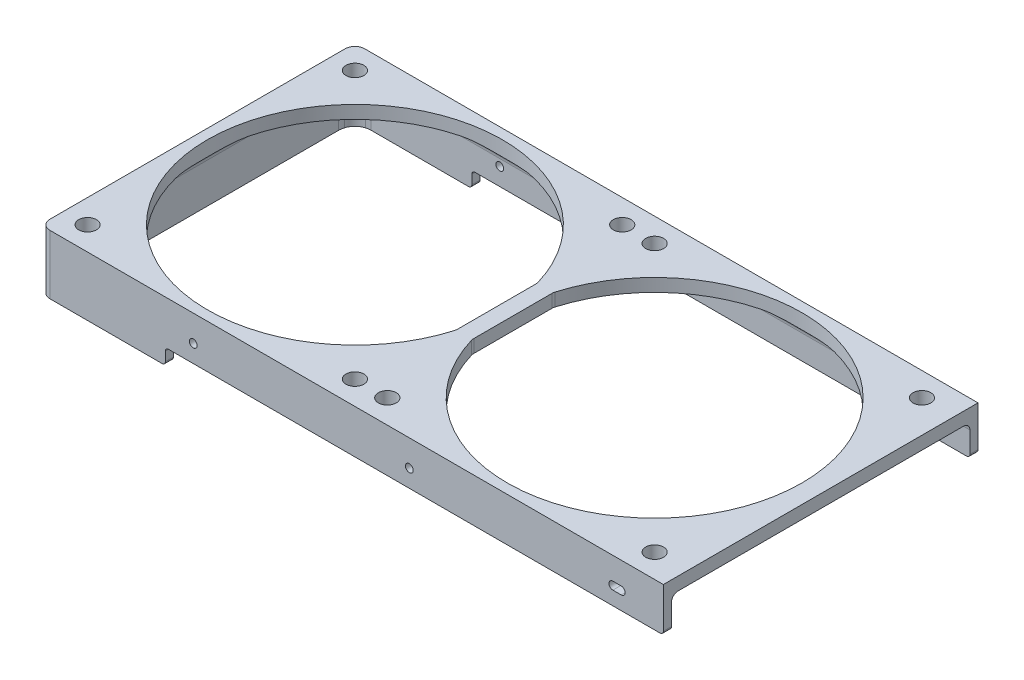
SolidWorks part; units mm, degrees
ref_plane "Front Plane" through (0, 0, 0) normal (0, 0, 1) x (1, 0, 0)
ref_plane "Top Plane" through (0, 0, 0) normal (0, 1, 0) x (1, 0, 0)
ref_plane "Right Plane" through (0, 0, 0) normal (1, 0, 0) x (0, 0, -1)
sketch "Sketch1" plane through (0, 0, 0) normal (0, 1, 0) x (1, 0, 0)
  line L1 (96.15, -48.55) -> (-96.15, -48.55)
  line L2 (96.15, -48.55) -> (96.15, 48.55)
  line L3 (96.15, 48.55) -> (-96.15, 48.55)
  line L4 (-96.15, -48.55) -> (-96.15, 48.55)
  line L5 (96.15, -48.55) -> (-96.15, 48.55) construction
  line L6 (96.15, 48.55) -> (-96.15, -48.55) construction
  point P0 (0, 0)
  dimension "D1" = 97.1
  dimension "D2" = 192.3
extrude "Boss-Extrude1" add sketch "Sketch1" along normal blind 13.5
sketch "Sketch2" plane through (0, 0, 0) normal (0, -1, 0) x (1, 0, 0)
  line L0 (96.15, 48.55) -> (96.15, -48.55) construction
  line L1 (96.15, 46.05) -> (-93.65, 46.05)
  line L2 (96.15, 46.05) -> (96.15, -46.05)
  line L3 (96.15, -46.05) -> (-93.65, -46.05)
  line L4 (-93.65, 46.05) -> (-93.65, -46.05)
  line L5 (-96.15, 48.55) -> (96.15, 48.55) construction
  line L6 (-96.15, -48.55) -> (-96.15, 48.55) construction
  line L7 (96.15, -48.55) -> (-96.15, -48.55) construction
  dimension "D1" = 2.5
  dimension "D2" = 2.5
  dimension "D3" = 2.5
extrude "Cut-Extrude1" cut sketch "Sketch2" against normal offset from surface (9.5 mm away) 4 up to face at (0, 13.5, 0)
fillet "Fillet1" radius 5 2 edges at (-93.65, 4.75, -46.05) (-93.65, 4.75, 46.05)
fillet "Fillet2" radius 2 5 edges at (3.75, 9.5, -46.05) (-92.1855, 9.5, -44.5855) (-93.65, 9.5, 0) (-92.1855, 9.5, 44.5855) (3.75, 9.5, 46.05)
sketch "Sketch3" plane through (0, 0, 0) normal (0, -1, 0) x (1, 0, 0)
  line L0 (-57.55, 48.55) -> (-57.55, 46.05)
  line L1 (-57.55, -46.05) -> (-57.55, -48.55)
  line L8 (-96.15, 48.55) -> (-96.15, -48.55)
  line L9 (-96.15, -48.55) -> (96.15, -48.55)
  line L10 (96.15, -48.55) -> (96.15, -46.05)
  line L11 (96.15, -46.05) -> (-88.65, -46.05)
  line L12 (-93.65, -41.05) -> (-93.65, 41.05)
  line L13 (-88.65, 46.05) -> (96.15, 46.05)
  line L14 (96.15, 46.05) -> (96.15, 48.55)
  line L15 (96.15, 48.55) -> (-96.15, 48.55)
  line L16 (-96.15, 48.55) -> (-96.15, -48.55)
  line L17 (-96.15, -48.55) -> (-57.55, -48.55)
  line L19 (-57.55, -46.05) -> (-88.65, -46.05)
  line L20 (-93.65, -41.05) -> (-93.65, 41.05)
  line L21 (-88.65, 46.05) -> (-57.55, 46.05)
  line L23 (-57.55, 48.55) -> (-96.15, 48.55)
  arc A5 (-93.65, -41.05) -> (-88.65, -46.05) centre (-88.65, -41.05) ccw
  arc A6 (-88.65, 46.05) -> (-93.65, 41.05) centre (-88.65, 41.05) ccw
  arc A9 (-93.65, -41.05) -> (-88.65, -46.05) centre (-88.65, -41.05) ccw
  arc A10 (-88.65, 46.05) -> (-93.65, 41.05) centre (-88.65, 41.05) ccw
  dimension "D2" = 38.6
  dimension "D1" = 0
extrude "Boss-Extrude2" add sketch "Sketch3" along normal blind 4.8
sketch "Sketch4" plane through (0, 9.5, 0) normal (0, -1, 0) x (1, 0, 0)
  line L0 (-47.6, 0) -> (44.9, 0) construction
  line L1 (-3.85, 12.4975) -> (-3.85, -12.4975)
  line L2 (1.15, 12.4975) -> (1.15, -12.4975)
  line L3 (-47.6, 0) -> (-88.85, 41.25) construction
  line L4 (-1.35, 0) -> (-1.35, 17.0754) construction
  arc A0 (-3.85, 12.4975) -> (-3.85, -12.4975) centre (-47.6, 0) ccw
  arc A1 (1.15, -12.4975) -> (1.15, 12.4975) centre (44.9, 0) ccw
  circle A2 centre (-88.85, 41.25) radius 2.75
  circle A3 centre (-6.35, 41.25) radius 2.75
  circle A4 centre (-6.35, -41.25) radius 2.75
  circle A5 centre (-88.85, -41.25) radius 2.75
  circle A6 centre (86.15, -41.25) radius 2.75
  circle A7 centre (3.65, -41.25) radius 2.75
  circle A8 centre (3.65, 41.25) radius 2.75
  circle A9 centre (86.15, 41.25) radius 2.75
  point P11 (-1.35, 49.225)
  point P12 (-47.6, 0)
  point P20 (-47.6, 0)
  dimension "D3" = 91
  dimension "D7" = 5.5
  dimension "D1" = 44.9
  dimension "D2" = 47.6
  dimension "D4" = 5
  dimension "D5" = 41.25
  dimension "D6" = 41.25
  dimension "D8" = 4
extrude "Cut-Extrude2" cut sketch "Sketch4" against normal through all both and the other way through all
fillet "Fillet4" radius 3 6 edges at (-96.15, 4.35, 48.55) (-96.15, 4.35, -48.55) (-3.85, 11.5, -12.4975) (-3.85, 11.5, 12.4975) (1.15, 11.5, 12.4975) (1.15, 11.5, -12.4975)
sketch "Sketch5" plane through (0, -4.8, 0) normal (0, -1, 0) x (1, 0, 0)
  circle A5 centre (-6.35, -41.25) radius 4.75
  circle A8 centre (3.65, -41.25) radius 4.75
  circle A11 centre (-88.85, -41.25) radius 4.75
  circle A12 centre (86.15, -41.25) radius 4.75
  circle A14 centre (86.15, 41.25) radius 4.75
  circle A17 centre (3.65, 41.25) radius 4.75
  circle A20 centre (-6.35, 41.25) radius 4.75
  circle A22 centre (-88.85, 41.25) radius 4.75
  circle A23 centre (86.15, -41.25) radius 2.75 construction
  dimension "D1" = 2
extrude "Cut-Extrude3" cut sketch "Sketch5" against normal up to surface (14.3 mm away) up to face at (86.15, 9.5, -38.5)
fillet "Fillet5" radius 1 6 edges at (-57.55, -4.8, -47.3) (-57.55, 0, -47.3) (-57.55, -4.8, 47.3) (-57.55, 0, 47.3) (96.15, 0, 47.3) (96.15, 0, -47.3)
hole_wizard "M2 Clearance Hole1" positions "Sketch8" profile "Sketch7" hole size "M2" standard "ANSI Metric" end condition through all
sketch "Sketch8" plane through (0, 0, 48.55) normal (0, 0, 1) x (1, 0, 0)
  line L0 (-56.55, 0) -> (95.15, 0) construction
  point P0 (-48.95, 5.4)
  point P2 (17.75, 5.4)
  point P7 (0, 0)
  point P11 (0, 0)
  dimension "D1" = 48.95
  dimension "D2" = 17.75
  dimension "D3" = 5.4
sketch "Sketch7" plane through (-48.95, 5.4, 48.55) normal (1, 0, 0) x (0, -1, 0)
  line L0 (0, 0) -> (0, 97.1)
  line L1 (0, 97.1) -> (1.2, 97.1)
  line L2 (1.2, 97.1) -> (1.2, 0)
  line L5 (1.2, 0) -> (0, 0)
  line L11 (0, -6.35) -> (0, 107.95) construction
  dimension "Thru Hole Dia." = 2.4
  dimension "Thru Hole Depth" = 97.1
hole_wizard "M2 Clearance Slot1" positions "Sketch9" profile "Sketch10" size "M2" standard "ANSI Metric" slot yes end condition up to next
sketch "Sketch9" plane through (0, 0, 48.55) normal (0, 0, 1) x (1, 0, 0)
  line L0 (79.35, 5.4) -> (84.35, 5.4) construction
  line L1 (17.75, 5.4) -> (81.85, 5.4) construction
  point P0 (81.85, 5.4)
  dimension "D1" = 5
  dimension "D2" = 64.1
sketch "Sketch10" plane through (81.85, 5.4, 48.55) normal (1, 0, 0) x (0, -1, 0)
  line L0 (0, 0) -> (0, 2.5)
  line L1 (0, 2.5) -> (1.2, 2.5)
  line L2 (1.2, 2.5) -> (1.2, 0)
  line L5 (1.2, 0) -> (0, 0)
  line L11 (0, -6.35) -> (0, 107.95) construction
  dimension "Thru Hole Dia." = 2.4
  dimension "Thru Hole Depth" = 2.5
hole_wizard "M2 Clearance Slot2" positions "Sketch11" profile "Sketch12" size "M2" standard "ANSI Metric" slot yes end condition up to next
sketch "Sketch11" plane through (0, 0, -48.55) normal (0, 0, -1) x (-1, 0, 0)
  line L0 (-78.65, 5.3913) -> (-73.65, 5.3913) construction
  line L1 (-76.15, 5.3913) -> (-17.75, 5.3913) construction
  circle A0 centre (-17.75, 5.4) radius 1.2 construction
  point P0 (-76.15, 5.3913)
  dimension "D1" = 5
  dimension "D2" = 58.4
sketch "Sketch12" plane through (76.15, 5.3913, -48.55) normal (1, 0, 0) x (0, 1, 0)
  line L0 (0, 0) -> (0, 2.5)
  line L1 (0, 2.5) -> (1.2, 2.5)
  line L2 (1.2, 2.5) -> (1.2, 0)
  line L5 (1.2, 0) -> (0, 0)
  line L11 (0, -6.35) -> (0, 107.95) construction
  dimension "Thru Hole Dia." = 2.4
  dimension "Thru Hole Depth" = 2.5
